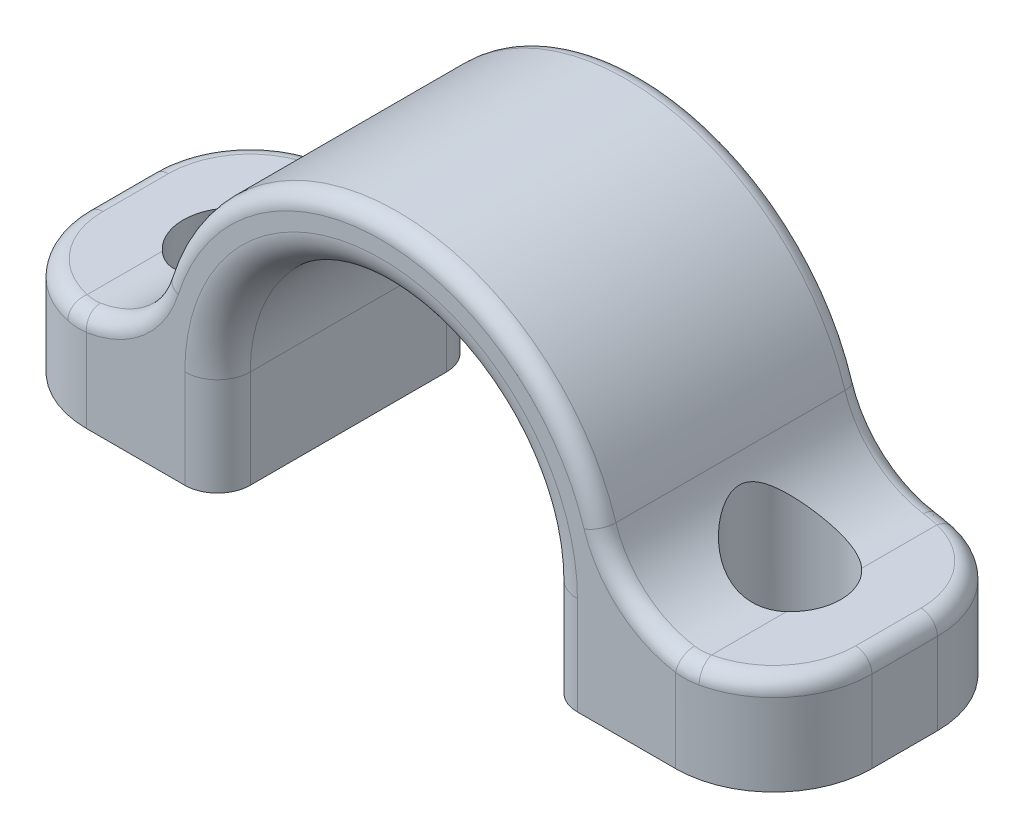
SolidWorks part; units mm, degrees
ref_plane "Front Plane" through (0, 0, 0) normal (0, 0, 1) x (1, 0, 0)
ref_plane "Top Plane" through (0, 0, 0) normal (0, 1, 0) x (1, 0, 0)
ref_plane "Right Plane" through (0, 0, 0) normal (1, 0, 0) x (0, 0, -1)
sketch "Sketch1" plane through (0, 0, 0) normal (0, 0, 1) x (1, 0, 0)
  line L0 (-9, 0) -> (9, 0)
  line L1 (-7, 1.5) -> (7, 1.5)
  line L2 (-12, 1.5) -> (12, 1.5)
  line L3 (-12, 1.5) -> (-12, -1.5)
  line L4 (-12, -1.5) -> (12, -1.5)
  line L5 (12, 1.5) -> (12, -1.5)
  line L6 (-12, 1.5) -> (12, -1.5) construction
  line L7 (-12, -1.5) -> (12, 1.5) construction
  line L8 (-5, 1.5) -> (5, 1.5)
  line L9 (-5, 1.5) -> (-5, -1.5)
  line L10 (-5, -1.5) -> (5, -1.5)
  line L11 (5, -1.5) -> (5, 1.5)
  arc A0 (-5, 1.5) -> (5, 1.5) centre (0, 1.5) cw
  arc A1 (-7, 1.5) -> (7, 1.5) centre (0, 1.5) cw
  point P0 (0, 0)
  point P4 (0, 0)
  point P13 (0, 1.5)
  point P16 (0, 1.5)
  dimension "D1" = 18
  dimension "D2" = 3
  dimension "D3" = 24
  dimension "D4" = 14
  dimension "D5" = 10
extrude "Boss-Extrude1" add sketch "Sketch1" along normal blind 8 contours A1 L1 A0 | L9 L1 L2 L3 L4 | L11 L4 L5 L2 L1 region at (-5.0762, -0.75, 0) region at (5.0762, 0.75, 0) region at (-6, 1.6565, 0)
sketch "Sketch2" plane through (0, -1.5, 0) normal (0, -1, 0) x (1, 0, 0)
  line L0 (-12, 8) -> (-8.5, 8)
  line L1 (-12, 8) -> (-5, 8) construction
  line L2 (-8.5, 8) -> (-8.5, 0)
  line L3 (-12, 0) -> (-5, 0) construction
  line L4 (12, 8) -> (8.5, 8)
  line L5 (5, 8) -> (12, 8) construction
  line L6 (8.5, 8) -> (8.5, 0)
  line L7 (5, 0) -> (12, 0) construction
  circle A0 centre (-8.5, 4) radius 1.55
  circle A1 centre (8.5, 4) radius 1.55
  dimension "D1" = 3.1
extrude "Cut-Extrude1" cut sketch "Sketch2" against normal through all contours A0 | A1
fillet "Fillet1" radius 3 2 edges at (-7, 1.5, 6.1953) (7, 1.5, 6.1953)
fillet "Fillet2" radius 3 4 edges at (-12, 0, 8) (-12, 0, 0) (12, 0, 8) (12, 0, 0)
fillet "Fillet3" radius 1 6 edges at (-5, 0, 8) (5, 0, 8) (-5, 0, 0) (5, 0, 0) (0, 6.5, 8) (0, 6.5, 0)
fillet "Fillet4" radius 0.5 16 edges at (-7.5535, 2.2514, 8) (-11.3041, 1.5, 6.9212) (-12, 1.5, 4) (-11.3041, 1.5, 1.0788) (-7.5535, 2.2514, 0) (0, 8.5, 0) (7.5535, 2.2514, 0) (11.3041, 1.5, 1.0788) (12, 1.5, 4) (11.3041, 1.5, 6.9212) (7.5535, 2.2514, 8) (0, 8.5, 8)
